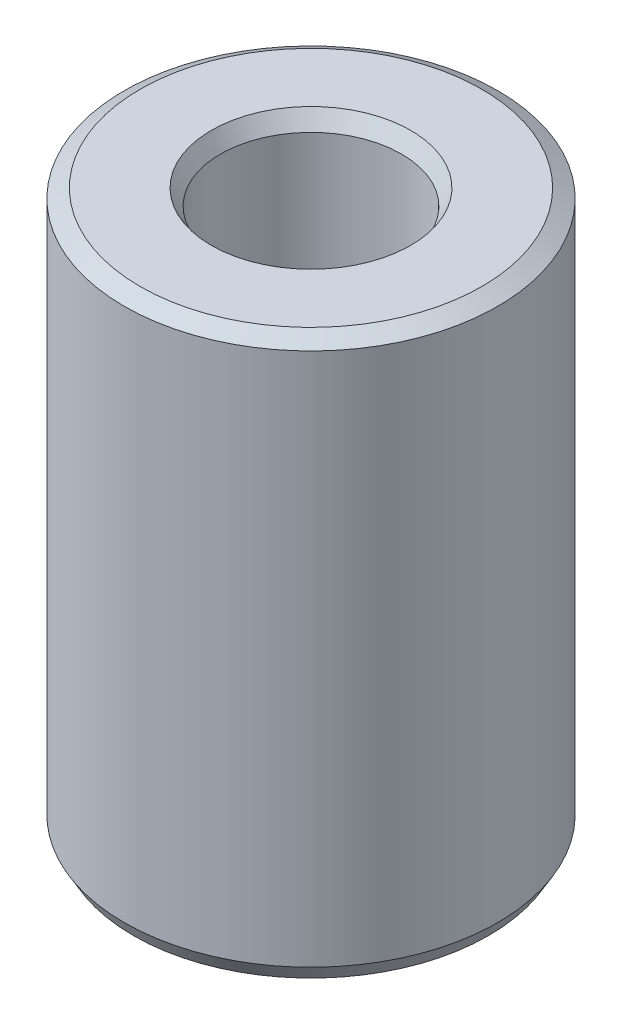
SolidWorks part; units mm, degrees
ref_plane "Front Plane" through (0, 0, 0) normal (0, 0, 1) x (1, 0, 0)
ref_plane "Top Plane" through (0, 0, 0) normal (0, 1, 0) x (1, 0, 0)
ref_plane "Right Plane" through (0, 0, 0) normal (1, 0, 0) x (0, 0, -1)
sketch "Sketch1" plane through (0, 0, 0) normal (0, 1, 0) x (1, 0, 0)
  circle A0 centre (0, 0) radius 7.5
  dimension "SLEEVE_OD" = 15
extrude "Boss-Extrude1" add sketch "Sketch1" along normal blind 22.4371
sketch "Sketch2" plane through (0, 0, 0) normal (0, 1, 0) x (1, 0, 0)
  circle A0 centre (0, 0) radius 3.6339
  dimension "BORE_D" = 7.2677
extrude "Cut-Extrude1" cut sketch "Sketch2" along normal through all
chamfer "Chamfer1" distance 0.3687 angle 60 4 edges at (0, 22.4371, 3.6339) (0, 0, 3.6339) (0, 0, 7.5) (0, 22.4371, 7.5) first distance on face at (0, 22.4371, 3.6339) first distance on face at (0, 0, 3.6339) first distance on face at (0, 22.4371, 7.5)
